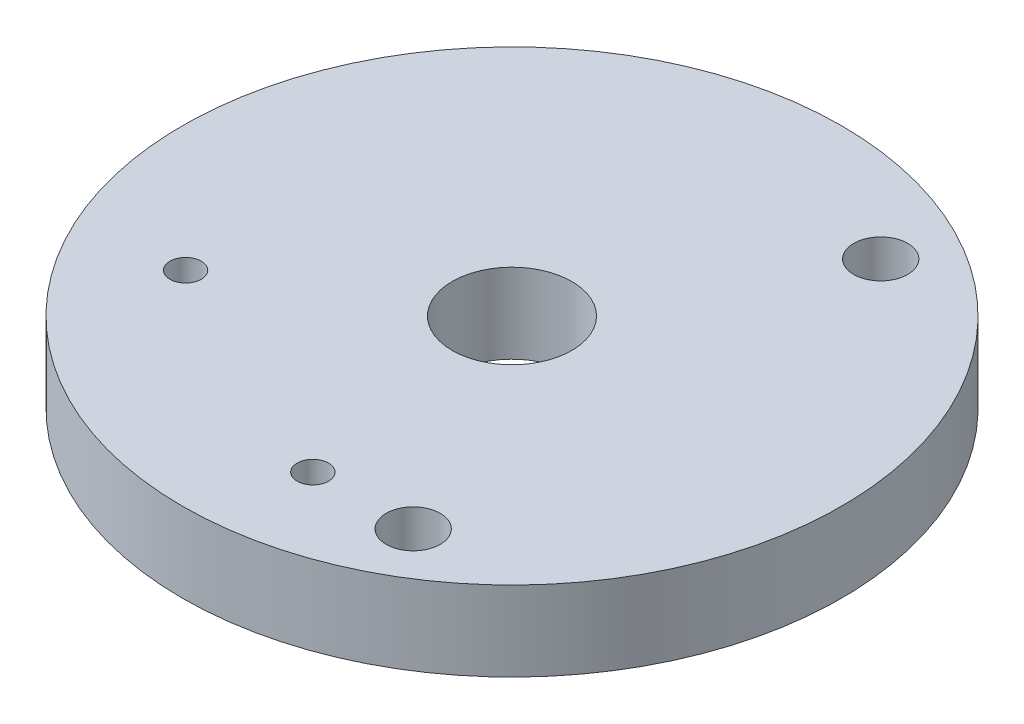
SolidWorks part; units mm, degrees
material "6061 Alloy"
ref_plane "Front Plane" through (0, 0, 0) normal (0, 0, 1) x (1, 0, 0)
ref_plane "Top Plane" through (0, 0, 0) normal (0, 1, 0) x (1, 0, 0)
ref_plane "Right Plane" through (0, 0, 0) normal (1, 0, 0) x (0, 0, -1)
sketch "Sketch1" plane through (0, 0, 0) normal (0, 1, 0) x (1, 0, 0)
  line L1 (-26.25, 26.25) -> (26.25, 26.25) construction
  line L2 (-26.25, 26.25) -> (-26.25, -38.75) construction
  line L3 (-26.25, -38.75) -> (26.25, -38.75) construction
  line L4 (26.25, 26.25) -> (26.25, -38.75) construction
  line L5 (-26.25, 26.25) -> (26.25, -38.75) construction
  line L6 (-26.25, -38.75) -> (26.25, 26.25) construction
  circle A2 centre (0, 0) radius 4.7625
  circle A3 centre (0, 0) radius 26.25
  point P4 (0, -6.25)
  dimension "D5" = 52.5
  dimension "D6" = 9.525
  dimension "D2" = 65
extrude "Boss-Extrude1" add sketch "Sketch1" along normal mid plane 6.35 contours L4 A3 L1 L2 L3 | A3 A2 region at (-25.5075, 0, 0)
hole_wizard "M4 Clearance Hole1" positions "Sketch6" profile "Sketch7" hole size "M4" standard "ANSI Metric" end condition up to next
sketch "Sketch6" plane through (0, 3.175, 0) normal (0, 1, 0) x (1, 0, 0)
  line L0 (0, 0) -> (10.75, 18.6195)
  line L1 (0, 0) -> (10.75, -18.6195)
  line L2 (0, 0) -> (-21.5, 0)
  point P2 (10.75, 18.6195)
  point P10 (10.75, -18.6195)
  dimension "D1" = 21.5
  dimension "D2" = 120
  dimension "D3" = 120
sketch "Sketch7" plane through (10.75, 3.175, 18.6195) normal (1, 0, 0) x (0, 0, 1)
  line L0 (0, 0) -> (0, 6.35)
  line L1 (0, 6.35) -> (2.15, 6.35)
  line L2 (2.15, 6.35) -> (2.15, 0)
  line L5 (2.15, 0) -> (0, 0)
  line L11 (0, -6.35) -> (0, 107.95) construction
  dimension "Thru Hole Dia." = 4.3
  dimension "Thru Hole Depth" = 6.35
hole_wizard "M3x0.5 Tapped Hole1" positions "Sketch8" profile "Sketch9" tap size "M3x0.5" standard "ANSI Metric" end condition up to next
sketch "Sketch8" plane through (0, 3.175, 0) normal (0, 1, 0) x (1, 0, 0)
  line L2 (-1000, 0) -> (49000, 0) construction
  line L3 (0, 0) -> (-6.6562, -14.2743) construction
  line L5 (-16.1543, -9.8453) -> (2.8419, -18.7034) construction
  point P20 (0, 0)
  point P47 (-16.1543, -9.8453)
  point P50 (2.8419, -18.7034)
  dimension "D1" = 15.75
  dimension "D2" = 25
  dimension "D3" = 20.96
sketch "Sketch9" plane through (0, 3.175, 0) normal (1, 0, 0) x (0, 0, 1)
  line L0 (0, 0) -> (0, 6.35)
  line L1 (0, 6.35) -> (1.25, 6.35)
  line L2 (1.25, 6.35) -> (1.25, 0)
  line L5 (1.25, 0) -> (0, 0)
  line L11 (0, -6.35) -> (0, 107.95) construction
  dimension "Thru Tap Drill Dia." = 2.5
  dimension "Thru Tap Drill Depth" = 6.35
cosmetic thread "Hole Thread1"
cosmetic thread "Hole Thread6"
